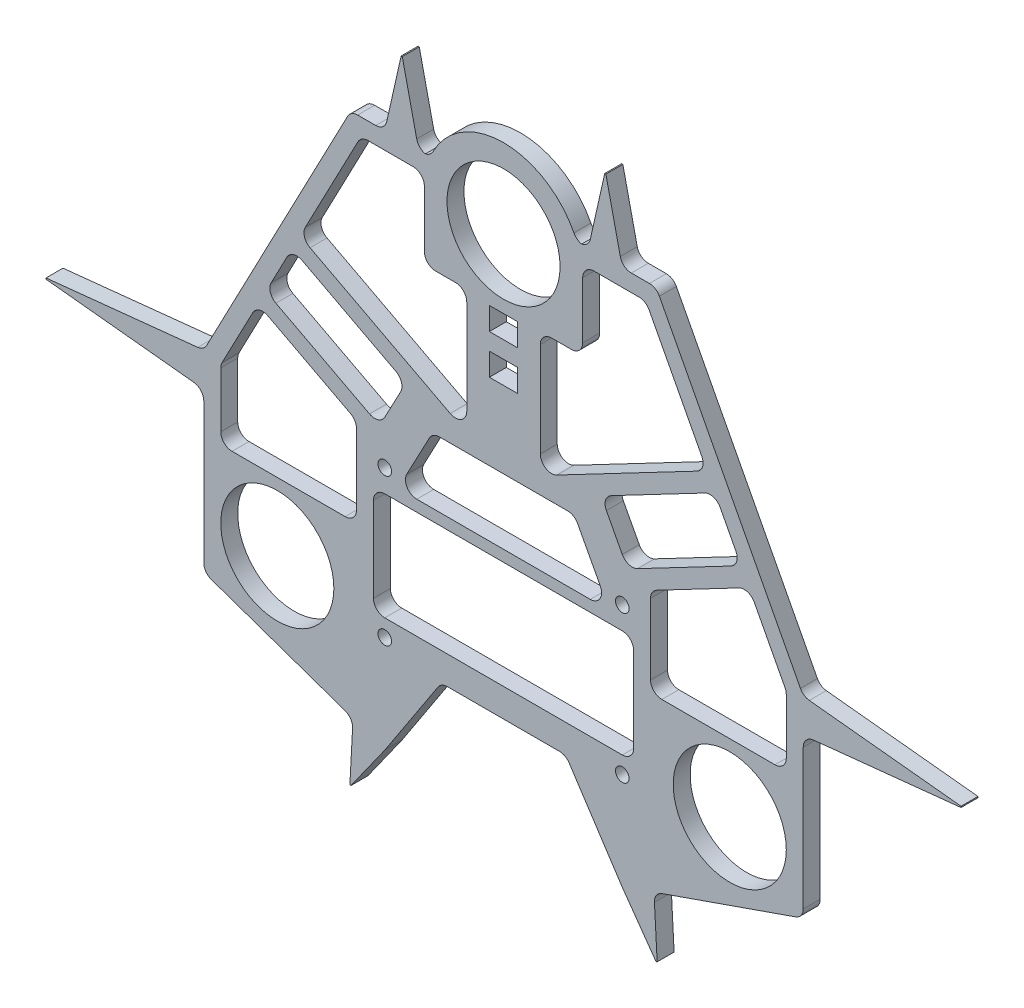
SolidWorks part; units mm, degrees
ref_plane "Plan de face" through (0, 0, 0) normal (0, 0, 1) x (1, 0, 0)
ref_plane "Plan de dessus" through (0, 0, 0) normal (0, 1, 0) x (1, 0, 0)
ref_plane "Plan de droite" through (0, 0, 0) normal (1, 0, 0) x (0, 0, -1)
sketch "Esquisse1" plane through (0, 0, 0) normal (0, 0, 1) x (1, 0, 0)
  line L0 (-40, 0) -> (40, 0) construction
  line L1 (40, 0) -> (0, 69.282) construction
  line L2 (0, 69.282) -> (-40, 0) construction
  line L3 (0, 0) -> (0, 69.282) construction
  line L12 (53, -24) -> (53, 25) construction
  line L13 (-53, 74.6) -> (53, 74.6) construction
  line L14 (-53, 74.6) -> (-53, -24) construction
  line L15 (-53, -24) -> (53, -24) construction
  line L16 (53, 74.6) -> (53, -24) construction
  line L17 (53, 25) -> (27, 74.6) construction
  line L18 (27, 74.6) -> (-27, 74.6) construction
  line L19 (-27, 74.6) -> (-53, 25) construction
  line L20 (-53, 25) -> (-53, -24) construction
  line L21 (40, 25) -> (-40, 25) construction
  line L22 (-40, 4) -> (40, 4) construction
  line L23 (-40, 4) -> (-40, -4) construction
  line L24 (-40, -4) -> (40, -4) construction
  line L25 (40, 4) -> (40, -4) construction
  line L26 (-34, 29) -> (34, 29) construction
  line L27 (-34, 29) -> (-34, 21) construction
  line L28 (-34, 21) -> (34, 21) construction
  line L29 (34, 29) -> (34, 21) construction
  line L30 (-4, 69.282) -> (4, 69.282) construction
  line L31 (-4, 69.282) -> (-4, -4) construction
  line L32 (-4, -4) -> (4, -4) construction
  line L33 (4, 69.282) -> (4, -4) construction
  line L34 (34, 39) -> (34, 11) construction
  line L81 (-27, 74.6) -> (27, 74.6) construction
  line L83 (53, 25) -> (53, -24) construction
  line L84 (53, -24) -> (-53, -24) construction
  line L85 (-53, -24) -> (-53, 25) construction
  line L103 (-53, -9) -> (-10, -24) construction
  line L104 (53, 25) -> (80.9, 22.1)
  line L105 (80.9, 22.1) -> (80.9, 21.9)
  line L106 (80.9, 21.9) -> (53, 19)
  line L107 (53, 19) -> (53, -9)
  line L108 (53, -9) -> (10, -24) construction
  line L109 (10, -24) -> (-10, -24) construction
  line L110 (-53, 19) -> (-53, -9)
  line L111 (-80.9, 21.9) -> (-53, 19)
  line L112 (-53, 25) -> (-80.9, 22.1)
  line L113 (-80.9, 22.1) -> (-80.9, 21.9)
  line L114 (53, 22) -> (80.9, 22) construction
  line L116 (21, 74.6) -> (18.1, 87.5)
  line L117 (18.1, 87.5) -> (17.9, 87.5)
  line L118 (17.9, 87.5) -> (15, 74.6)
  line L119 (15, 74.6) -> (-15, 74.6) construction
  line L120 (15, 74.6) -> (21, 74.6) construction
  line L121 (18, 74.6) -> (18, 87.5) construction
  line L122 (-17.9, 87.5) -> (-15, 74.6)
  line L123 (-18.1, 87.5) -> (-17.9, 87.5)
  line L124 (-21, 74.6) -> (-18.1, 87.5)
  line L126 (-15, 74.6) -> (-12.9506, 74.6)
  line L127 (15, 74.6) -> (12.9506, 74.6)
  line L128 (-53, -9) -> (-20, -20.5116) construction
  line L131 (20, -20.5116) -> (53, -9) construction
  line L132 (-20, -20.5116) -> (20, -20.5116) construction
  line L133 (53, -9) -> (26.6094, -18.206)
  line L134 (26.6094, -18.206) -> (27.1649, -28.6032)
  line L135 (27.1649, -28.6032) -> (26.9761, -28.6691)
  line L136 (26.9761, -28.6691) -> (20.9442, -20.1823)
  line L138 (-53, -9) -> (-26.6094, -18.206)
  line L139 (-26.6094, -18.206) -> (-27.1649, -28.6032)
  line L140 (-27.1649, -28.6032) -> (-26.9761, -28.6691)
  line L141 (-26.9761, -28.6691) -> (-20.9442, -20.1823)
  line L143 (20.9442, -20.1823) -> (26.6094, -18.206) construction
  line L144 (23.7768, -19.1941) -> (27.0705, -28.6361) construction
  line L145 (-40, 0) -> (20, 34.641) construction
  line L146 (40, 0) -> (-20, 34.641) construction
  line L147 (-2.5, 53.094) -> (2.5, 53.094)
  line L148 (-2.5, 57.094) -> (2.5, 57.094)
  line L149 (-2.5, 57.094) -> (-2.5, 53.094)
  line L151 (2.5, 57.094) -> (2.5, 53.094)
  line L196 (-47, 23) -> (-47, 13) construction
  line L197 (-14, 56.094) -> (-7, 56.094) construction
  line L202 (14.0909, -20.5116) -> (-20, -20.5116)
  line L211 (21, 23) -> (-21, 23) construction
  line L227 (-2.5, 50.094) -> (2.5, 50.094)
  line L228 (2.5, 50.094) -> (2.5, 46.094)
  line L229 (2.5, 46.094) -> (-2.5, 46.094)
  line L230 (-2.5, 46.094) -> (-2.5, 50.094)
  line L231 (21, 74.6) -> (27, 74.6)
  line L232 (17.2502, 37.793) -> (37.3765, 48.3431) construction
  line L233 (-11, -5) -> (11, -5)
  line L234 (-11, -5) -> (-20.9442, -20.1823)
  line L235 (11, -5) -> (20.9442, -20.1823)
  line L236 (27, 74.6) -> (53, 25)
  line L237 (21.6982, 29.3986) -> (20.7618, 31.1659) construction
  line L238 (-21, 74.6) -> (-27, 74.6)
  line L239 (40.9789, 39.0491) -> (22.3741, 29.1909) construction
  line L240 (21.9323, 28.9568) -> (17.2502, 37.793)
  line L241 (17.692, 38.0271) -> (35.811, 47.6279) construction
  line L242 (18.4207, 35.584) -> (17.4843, 37.3512) construction
  line L243 (-27, 74.6) -> (-53, 25)
  line L245 (-21.9323, 28.9568) -> (-17.2502, 37.793)
  line L246 (17.2502, 37.793) -> (37.3765, 48.3431)
  line L247 (-21, 74.6) -> (-18.1, 87.5)
  line L248 (-17.9, 87.5) -> (-15, 74.6)
  line L249 (37.3765, 48.3431) -> (42.0192, 39.4862)
  line L250 (42.0192, 39.4862) -> (21.9323, 28.9568)
  line L251 (14, 71.6) -> (25.1854, 71.6)
  line L252 (25.1854, 71.6) -> (35.9837, 51.0002)
  line L253 (35.9837, 51.0002) -> (6.5, 35.545)
  line L254 (6.5, 35.545) -> (6.5, 57.6)
  line L255 (6.5, 57.6) -> (14, 57.6)
  line L256 (14, 57.6) -> (14, 71.6)
  line L257 (43.412, 36.8292) -> (50, 24.2614)
  line L258 (50, 24.2614) -> (50, 12)
  line L259 (50, 12) -> (26, 12)
  line L260 (26, 12) -> (26, 27.7019)
  line L261 (26, 27.7019) -> (43.412, 36.8292)
  line L262 (-23, 19) -> (23, 19)
  line L263 (23, 19) -> (23, 0)
  line L264 (23, 0) -> (-23, 0)
  line L265 (-23, 0) -> (-23, 19)
  line L266 (-26, 27.7019) -> (-43.412, 36.8292)
  line L267 (-26, 12) -> (-26, 27.7019)
  line L268 (-50, 12) -> (-26, 12)
  line L269 (-50, 24.2614) -> (-50, 12)
  line L270 (-43.412, 36.8292) -> (-50, 24.2614)
  line L271 (-42.0192, 39.4862) -> (-21.9323, 28.9568)
  line L273 (-37.3765, 48.3431) -> (-42.0192, 39.4862)
  line L274 (-17.2502, 37.793) -> (-37.3765, 48.3431)
  line L275 (-14, 71.6) -> (-25.1854, 71.6)
  line L276 (-14, 57.6) -> (-14, 71.6)
  line L277 (-6.5, 57.6) -> (-14, 57.6)
  line L278 (-6.5, 35.545) -> (-6.5, 57.6)
  line L279 (-35.9837, 51.0002) -> (-6.5, 35.545)
  line L280 (-25.1854, 71.6) -> (-35.9837, 51.0002)
  line L281 (-18.6646, 21) -> (-12.5472, 32.545)
  line L282 (-12.5472, 32.545) -> (12.5472, 32.545)
  line L283 (12.5472, 32.545) -> (18.6646, 21)
  line L284 (18.6646, 21) -> (-18.6646, 21)
  circle A0 centre (40, 0) radius 10 construction
  circle A1 centre (-40, 0) radius 10 construction
  circle A2 centre (0, 69.282) radius 10 construction
  circle A11 centre (-21, 23) radius 1.2
  circle A13 centre (21, 23) radius 1.2
  circle A14 centre (-40, 0) radius 10
  circle A15 centre (40, 0) radius 10
  circle A16 centre (0, 69.282) radius 10
  arc A17 (-12.9506, 74.6) -> (12.9506, 74.6) centre (0, 69.282) cw
  circle A39 centre (21, -3) radius 1.2
  circle A40 centre (21, -3) radius 2 construction
  circle A41 centre (-21, -3) radius 1.2
  point P18 (-25.25, -20)
  point P21 (-25.25, 50.5)
  point P24 (25.25, 50.5)
  point P74 (11.7205, 32.545)
  point P87 (0, 0)
  point P88 (0, 0)
  point P89 (0, 0)
  point P113 (0, -24)
  point P126 (0, 74.6)
  point P146 (0, 23.094)
  point P162 (0, 50.5)
  point P168 (0, 44.4936)
  point P171 (0, 50.5)
  point P196 (0, -5)
  point P198 (0, -12.6457)
  dimension "D5" = 20
  dimension "D36" = 20
  dimension "D7" = 2.4
  dimension "D2" = 80
  dimension "D3" = 50.5
  dimension "D4" = 70.5
  dimension "D9" = 106
  dimension "D10" = 106
  dimension "D11" = 98.6
  dimension "D12" = 24
  dimension "D14" = 54
  dimension "D17" = 8
  dimension "D18" = 8
  dimension "D19" = 8
  dimension "D20" = 8
  dimension "D22" = 25
  dimension "D23" = 34
  dimension "D24" = 90
  dimension "D35" = 49
  dimension "D37" = 10
  dimension "D38" = 15
  dimension "D41" = 3
  dimension "D42" = 3
  dimension "D44" = 6
  dimension "D45" = 12.9
  dimension "D46" = 18
  dimension "D47" = 4
  dimension "D40" = 27.9
  dimension "D48" = 40
  dimension "D49" = 0.2
  dimension "D50" = 6
  dimension "D51" = 4
  dimension "D52" = 10
  dimension "D39" = 5
  dimension "D43" = 5
  dimension "D53" = 4
  dimension "D34" = 30
  dimension "D56" = 10
  dimension "D57" = 37
  dimension "D58" = 47
  dimension "D63" = 33
  dimension "D64" = 14
  dimension "D65" = 7
  dimension "D30" = 23
  dimension "D29" = 42
  dimension "D31" = 3
  dimension "D8" = 180
  dimension "D13" = 46
  dimension "D15" = 46
  dimension "D26" = 12
  dimension "D27" = 3
  dimension "D28" = 5
  dimension "D32" = 4
  dimension "D33" = 14
  dimension "D55" = 14
  dimension "D16" = 3
  dimension "D25" = 3
  dimension "D54" = 3
  dimension "D59" = 54
  dimension "D60" = 3
  dimension "D61" = 3
  dimension "D62" = 3
  dimension "D66" = 3
  dimension "D67" = 3
  dimension "D68" = 37.3292
  dimension "D21" = 2
  dimension "D69" = 22
extrude "Boss.-Extru.1" add sketch "Esquisse1" along normal blind 3 contours A17 L126 L122 L123 L124 L238 L243 L112 L113 L111 L110 L138 L139 L140 L141 L234 L233 L235 L136 L135 L134 L133 L107 L106 L105 L104 L236 L231 L116 L117 L118 L127 A13 A11 L280 L275 L276 L277 L278 L279 L273 L270 L266 region at (66.7441, 21.5688, 0)
fillet "Congé1" radius 2 56 edges at (23, 0, 1.5) (23, 19, 1.5) (-27, 74.6, 1.5) (-21, 74.6, 1.5) (-12.9506, 74.6, 1.5) (-15, 74.6, 1.5) (12.9506, 74.6, 1.5) (15, 74.6, 1.5) (21, 74.6, 1.5) (53, 19, 1.5) (53, -9, 1.5) (11, -5, 1.5) (26.6094, -18.206, 1.5) (26, 12, 1.5) (50, 12, 1.5) (50, 24.2614, 1.5) (53, 25, 1.5) (17.2502, 37.793, 1.5) (21.9323, 28.9568, 1.5) (26, 27.7019, 1.5) (43.412, 36.8292, 1.5) (42.0192, 39.4862, 1.5) (37.3765, 48.3431, 1.5) (35.9837, 51.0002, 1.5) (27, 74.6, 1.5) (25.1854, 71.6, 1.5) (14, 57.6, 1.5) (14, 71.6, 1.5) (-14, 71.6, 1.5) (-14, 57.6, 1.5) (-6.5, 57.6, 1.5) (6.5, 57.6, 1.5) (6.5, 35.545, 1.5) (12.5472, 32.545, 1.5) (18.6646, 21, 1.5) (-18.6646, 21, 1.5) (-12.5472, 32.545, 1.5) (-6.5, 35.545, 1.5) (-17.2502, 37.793, 1.5) (-21.9323, 28.9568, 1.5) (-26, 27.7019, 1.5) (-26, 12, 1.5) (-23, 19, 1.5) (-23, 0, 1.5) (-11, -5, 1.5) (-26.6094, -18.206, 1.5) (-53, -9, 1.5) (-50, 12, 1.5) (-53, 19, 1.5) (-53, 25, 1.5) (-50, 24.2614, 1.5) (-43.412, 36.8292, 1.5) (-42.0192, 39.4862, 1.5) (-37.3765, 48.3431, 1.5) (-35.9837, 51.0002, 1.5) (-25.1854, 71.6, 1.5)
equation "\"D16@Esquisse1\"=\"D27@Esquisse1\""
equation "\"D25@Esquisse1\"=\"D27@Esquisse1\""
equation "\"D54@Esquisse1\"=\"D27@Esquisse1\""
equation "\"D60@Esquisse1\"=\"D27@Esquisse1\""
equation "\"D61@Esquisse1\"=\"D27@Esquisse1\""
equation "\"D62@Esquisse1\"=\"D27@Esquisse1\""
equation "\"D66@Esquisse1\"=\"D27@Esquisse1\""
equation "\"D67@Esquisse1\"=\"D27@Esquisse1\""
